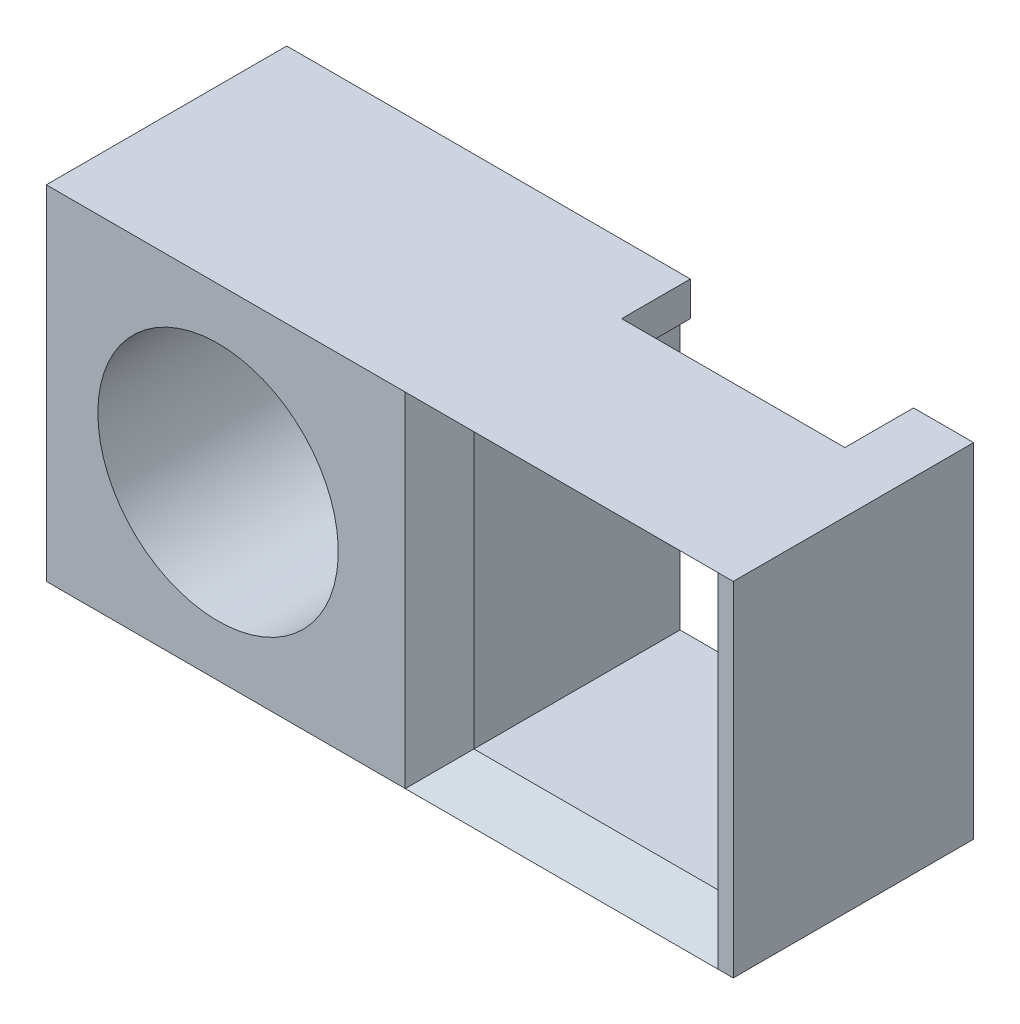
SolidWorks part; units mm, degrees
ref_plane "Alzado" through (0, 0, 0) normal (0, 0, 1) x (1, 0, 0)
ref_plane "Planta" through (0, 0, 0) normal (0, 1, 0) x (1, 0, 0)
ref_plane "Vista lateral" through (0, 0, 0) normal (1, 0, 0) x (0, 0, -1)
sketch "Croquis1" plane through (0, 0, 0) normal (0, 0, 1) x (1, 0, 0)
  line L1 (-6.3094, 6.7346) -> (13.6906, 6.7346)
  line L2 (-6.3094, 6.7346) -> (-6.3094, -3.2654)
  line L3 (-6.3094, -3.2654) -> (13.6906, -3.2654)
  line L4 (13.6906, 6.7346) -> (13.6906, -3.2654)
  point P4 (3.6906, 1.7346)
  point P5 (0, 0)
  point P6 (0, 0)
  dimension "D1" = 20
  dimension "D2" = 10
  dimension "D3" = 10
  dimension "D4" = 5
extrude "Saliente-Extruir1" add sketch "Croquis1" along normal blind 7
sketch "Croquis2" plane through (0, 0, 0) normal (0, 0, -1) x (-1, 0, 0)
  line L0 (-13.6906, 1.7346) -> (-3.6906, 1.7346) construction
  line L2 (1.3094, 6.7346) -> (1.3094, 1.7346) construction
  line L3 (-3.6906, 6.7346) -> (-3.6906, -3.2654) construction
  line L4 (-13.6906, 6.7346) -> (6.3094, 6.7346) construction
  line L5 (6.3094, -3.2654) -> (-13.6906, -3.2654) construction
  line L6 (-13.6906, -3.2654) -> (-13.6906, 6.7346) construction
  line L7 (-3.6906, 1.7346) -> (6.3094, 1.7346) construction
  line L8 (6.3094, 6.7346) -> (6.3094, -3.2654) construction
  line L9 (1.3094, 1.7346) -> (6.3094, 1.7346) construction
  line L10 (-12.2406, -2.2654) -> (-5.1406, -2.2654)
  line L11 (-12.2406, -2.2654) -> (-12.2406, 5.7346)
  line L12 (-12.2406, 5.7346) -> (-5.1406, 5.7346)
  line L13 (-5.1406, -2.2654) -> (-5.1406, 5.7346)
  line L14 (-12.2406, -2.2654) -> (-5.1406, 5.7346) construction
  line L15 (-12.2406, 5.7346) -> (-5.1406, -2.2654) construction
  circle A0 centre (1.3094, 1.7346) radius 3.5
  point P15 (-8.6906, 1.7346)
  dimension "D1" = 7.1
  dimension "D6" = 7
  dimension "D2" = 8
  dimension "D3" = 5
extrude "Cortar-Extruir2" cut sketch "Croquis2" against normal blind 7 contours L11 L10 L13 L12 | A0
sketch "Croquis7" plane through (0, 6.7346, 0) normal (0, 1, 0) x (1, 0, 0)
  line L0 (13.6906, 0) -> (5.4406, 0) construction
  line L1 (13.6906, 0) -> (-6.3094, 0) construction
  line L2 (5.4406, 0) -> (5.4406, -2) construction
  line L3 (13.6906, -7) -> (13.6906, 0) construction
  line L4 (11.9406, -2) -> (11.9406, 0) construction
  line L5 (5.4406, -2) -> (11.9406, -2)
  line L6 (5.4406, -2) -> (5.4406, 0)
  line L7 (5.4406, 0) -> (11.9406, 0)
  line L8 (11.9406, -2) -> (11.9406, 0)
  line L9 (5.4406, -2) -> (11.9406, 0) construction
  line L10 (5.4406, 0) -> (11.9406, -2) construction
  point P5 (5.4406, -1)
  point P9 (8.6906, -1)
  dimension "D1" = 6.5
  dimension "D2" = 2
  dimension "D3" = 8.25
extrude "Cortar-Extruir3" cut sketch "Croquis7" against normal blind 3
chamfer "Chaflán1" distance 1 angle 45 4 edges at (8.6906, 5.7346, 7) (5.1406, 1.7346, 7) (12.2406, 1.7346, 7) (8.6906, -2.2654, 7)
